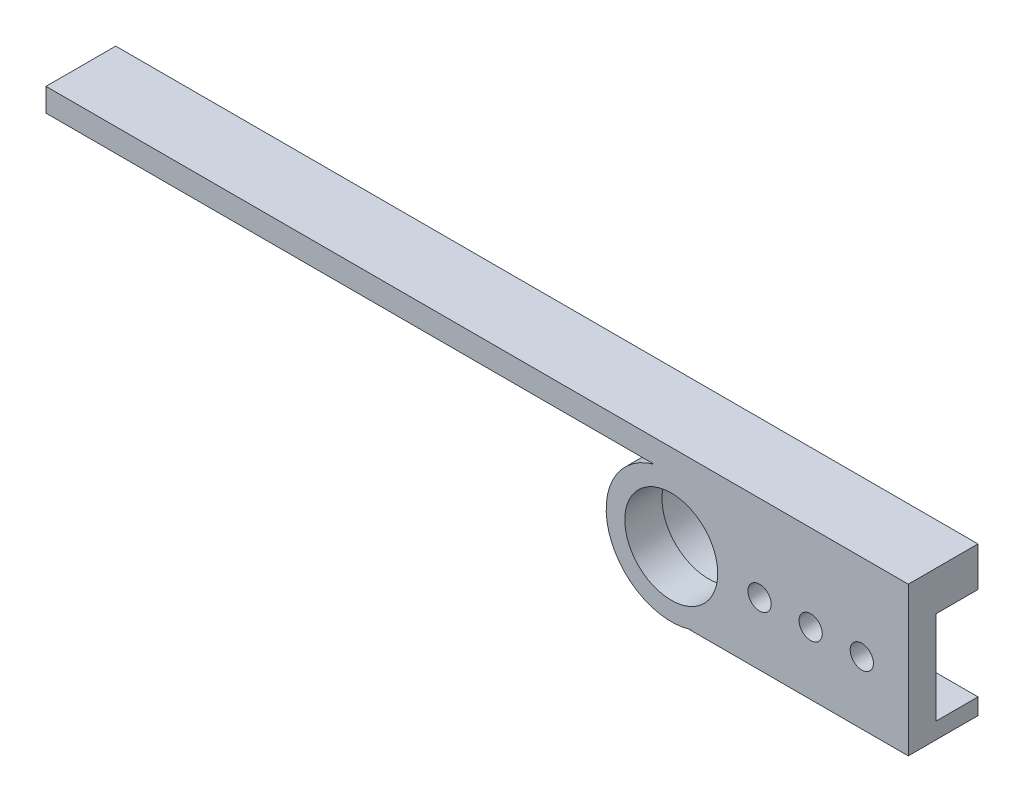
SolidWorks part; units mm, degrees
ref_plane "前视基准面" through (0, 0, 0) normal (0, 0, 1) x (1, 0, 0)
ref_plane "上视基准面" through (0, 0, 0) normal (0, 1, 0) x (1, 0, 0)
ref_plane "右视基准面" through (0, 0, 0) normal (1, 0, 0) x (0, 0, -1)
sketch "草图1" plane through (0, 0, 0) normal (0, 0, 1) x (1, 0, 0)
  line L1 (20, -10) -> (-20, -10)
  line L2 (20, -10) -> (20, 10)
  line L3 (20, 10) -> (-20, 10)
  line L4 (-20, -10) -> (-20, 10)
  line L5 (20, -10) -> (-20, 10) construction
  line L6 (20, 10) -> (-20, -10) construction
  point P0 (0, 0)
  dimension "D1" = 40
  dimension "D2" = 20
extrude "凸台-拉伸1" add sketch "草图1" along normal blind 6
sketch "草图2" plane through (0, 0, 6) normal (0, 0, 1) x (1, 0, 0)
  line L0 (20, -10) -> (20, 10) construction
  circle A0 centre (10, 0) radius 2.5
  circle A1 centre (-1, 0) radius 2.5
  circle A2 centre (-12, 0) radius 2.5
  dimension "D1" = 10
  dimension "D2" = 5
  dimension "D3" = 3
extrude "切除-拉伸1" cut sketch "草图2" against normal through all
sketch "草图3" plane through (0, 0, 6) normal (0, 0, 1) x (1, 0, 0)
  line L0 (20, 13.5) -> (20, 10)
  line L1 (20, -13.5) -> (-26.894, -13.5)
  line L3 (20, 13.5) -> (-26.894, 13.5)
  line L4 (-20, 10) -> (-20, -10)
  line L5 (-20, -10) -> (20, -10)
  line L6 (20, -10) -> (20, 10)
  line L7 (20, 10) -> (-20, 10)
  line L8 (-20, 10) -> (-20, -10)
  line L9 (-20, -10) -> (20, -10)
  line L10 (20, -10) -> (20, 10)
  line L11 (20, 10) -> (-20, 10)
  line L12 (-26.894, -13.5) -> (-26.894, 13.5)
  line L13 (20, -10.0394) -> (-26.894, 13.5) construction
  line L14 (20, 10.0394) -> (-26.894, -13.5) construction
  line L15 (20, -10) -> (20, -13.5)
  circle A0 centre (-31, 0) radius 11
  circle A1 centre (-31, 0) radius 14
  point P2 (0, 0)
  line M10 (-20, 10) -> (-20, -10)
  line M11 (-20, -10) -> (20, -10)
  line M13 (20, 10) -> (-20, 10)
  dimension "D3" = 22
  dimension "D4" = 28
  dimension "D2" = 3.5
  dimension "D1" = 0
extrude "凸台-拉伸2" add sketch "草图3" against normal blind 15 contours L3 A1 L1 L12 A0 | A1 L1 L15 M11 M10 | L1 A1 L8 A0 L12 | L8 A1 L3 L12 A0 | L8 A1 | A1 L0 L3 M10 M13 region at (-1.9449, 11.7771, 6) region at (-1.9449, -11.7771, 6) region at (-23.0173, 9.0328, 6) region at (-27.2274, 11.7946, 6) region at (-18.7882, 0, 6) region at (-23.0173, -9.0328, 6)
sketch "草图5" plane through (0, 0, 6) normal (0, 0, 1) x (1, 0, 0)
  circle A0 centre (-31, 0) radius 10
  circle A1 centre (-31, 0) radius 11 construction
  circle A2 centre (-31, 0) radius 11
  dimension "D1" = 20
extrude "凸台-拉伸3" add sketch "草图5" against normal blind 8
sketch "草图6" plane through (0, 0, 6) normal (0, 0, 1) x (1, 0, 0)
  circle A0 centre (-31, 0) radius 8.5
  circle A1 centre (-31, 0) radius 10 construction
  circle A2 centre (-31, 0) radius 10
  dimension "D1" = 17
sketch "草图7" plane through (0, 13.5, 0) normal (0, 1, 0) x (1, 0, 0)
  circle A0 centre (-17.1666, 1.953) radius 2.6594
sketch "草图8" plane through (20, 0, 0) normal (1, 0, 0) x (0, 0, -1)
  line L1 (-6, 13.5) -> (9, 13.5)
  line L2 (-6, 13.5) -> (-6, 18.5)
  line L3 (-6, 18.5) -> (9, 18.5)
  line L4 (9, 13.5) -> (9, 18.5)
  dimension "D1" = 5
extrude "凸台-拉伸4" add sketch "草图8" against normal blind 500
sketch "草图9" plane through (0, 0, -9) normal (0, 0, -1) x (-1, 0, 0)
  line L1 (24.4567, 15.8334) -> (28.494, 15.8334)
  line L2 (24.4567, 15.8334) -> (24.4567, 12.469)
  line L3 (24.4567, 12.469) -> (28.494, 12.469)
  line L4 (28.494, 15.8334) -> (28.494, 12.469)
extrude "凸台-拉伸5" add sketch "草图9" against normal through all
sketch "草图10" plane through (0, 18.5, 0) normal (0, 1, 0) x (1, 0, 0)
  line L0 (-165.5205, -217.2089) -> (-165.5205, 9)
  line L1 (-165.5205, -217.2089) -> (-39.8292, -217.2089) construction
  line L2 (-165.5205, 139.2909) -> (-165.5205, -230.7091) construction
  line L3 (-480, 9) -> (20, 9) construction
sketch "草图11" plane through (0, 18.5, 0) normal (0, 1, 0) x (1, 0, 0)
  line L1 (-165.5205, -217.2089) -> (-495.6366, -217.2089)
  line L2 (-165.5205, -217.2089) -> (-165.5205, 25.3653)
  line L3 (-165.5205, 25.3653) -> (-495.6366, 25.3653)
  line L4 (-495.6366, -217.2089) -> (-495.6366, 25.3653)
extrude "切除-拉伸2" cut sketch "草图11" against normal through all
sketch "草图12" plane through (-480, 0, 0) normal (-1, 0, 0) x (0, 0, 1)
  line L4 (3.8295, 18.5) -> (3.8295, 13.5)
  line L5 (3.8295, 13.5) -> (6, 13.5)
  line L6 (6, 13.5) -> (6, 18.5)
  line L7 (6, 18.5) -> (3.8295, 18.5)
  line L8 (3.8295, 18.5) -> (3.8295, 13.5)
  line L9 (3.8295, 13.5) -> (6, 13.5)
  line L10 (6, 13.5) -> (6, 18.5)
  line L11 (6, 18.5) -> (3.8295, 18.5)
  dimension "D1" = 0
extrude "切除-拉伸3" cut sketch "草图12" against normal up to surface (314.4795 mm away) rebuild error yes up to face at (-165.5205, 16, -1.5)
